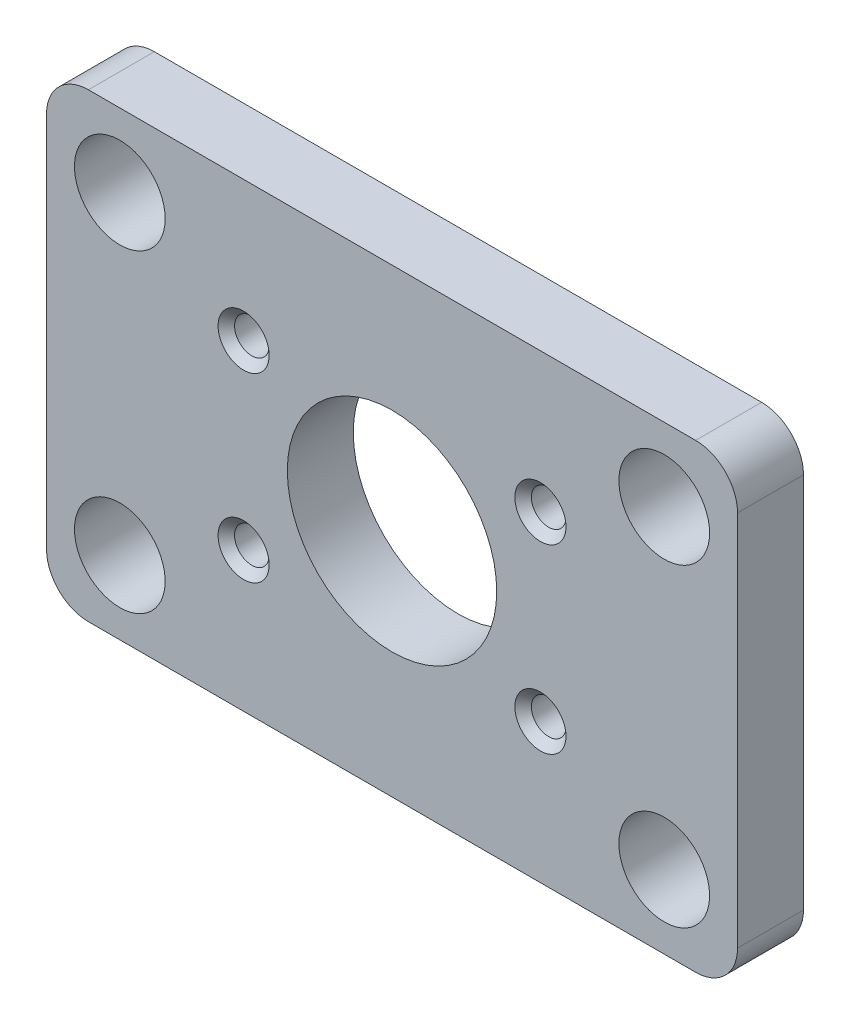
SolidWorks part; units mm, degrees
ref_plane "Front Plane" through (0, 0, 0) normal (0, 0, 1) x (1, 0, 0)
ref_plane "Top Plane" through (0, 0, 0) normal (0, 1, 0) x (1, 0, 0)
ref_plane "Right Plane" through (0, 0, 0) normal (1, 0, 0) x (0, 0, -1)
sketch "Sketch1" plane through (0, 0, 0) normal (0, 0, 1) x (1, 0, 0)
  line L0 (0, 0) -> (-20.955, 0) construction
  line L1 (20.955, -13.97) -> (-20.955, -13.97)
  line L2 (20.955, -13.97) -> (20.955, 13.97)
  line L3 (20.955, 13.97) -> (-20.955, 13.97)
  line L4 (-20.955, -13.97) -> (-20.955, 13.97)
  line L5 (20.955, -13.97) -> (-20.955, 13.97) construction
  line L6 (20.955, 13.97) -> (-20.955, -13.97) construction
  line L7 (0, 0) -> (0, 13.97) construction
  line L8 (-9.0005, 5.5004) -> (9.0005, 5.5004) construction
  line L9 (9.0005, 5.5004) -> (9.0005, -5.5004) construction
  circle A0 centre (-16.51, 9.525) radius 2.75
  circle A1 centre (16.51, 9.525) radius 2.75
  circle A2 centre (16.51, -9.525) radius 2.75
  circle A3 centre (-16.51, -9.525) radius 2.75
  circle A4 centre (-9.0005, 5.5004) radius 1.05
  circle A5 centre (9.0005, -5.5004) radius 1.05
  circle A6 centre (0, 0) radius 6.35
  circle A7 centre (-9.0005, -5.5004) radius 1.05
  circle A8 centre (9.0005, 5.5004) radius 1.05
  point P0 (0, 0)
  point P22 (0, 5.5004)
  point P24 (9.0005, 0)
  point P29 (-16.51, 9.525)
  point P30 (16.51, 9.525)
  point P31 (16.51, -9.525)
  point P32 (-16.51, -9.525)
  dimension "D3" = 5.5
  dimension "D6" = 2.1
  dimension "D9" = 12.7
  dimension "D1" = 27.94
  dimension "D2" = 41.91
  dimension "D4" = 19.05
  dimension "D5" = 33.02
  dimension "D7" = 18.001
  dimension "D8" = 11.0007
extrude "Boss-Extrude1" add sketch "Sketch1" along normal blind 4
fillet "Fillet1" radius 2.54 4 edges at (20.955, 13.97, 2) (20.955, -13.97, 2) (-20.955, -13.97, 2) (-20.955, 13.97, 2)
chamfer "Chamfer1" distance 0.5 angle 45 4 edges at (10.0505, -5.5004, 4) (7.9505, 5.5004, 4) (-10.0505, -5.5004, 4) (-7.9505, 5.5004, 4)
